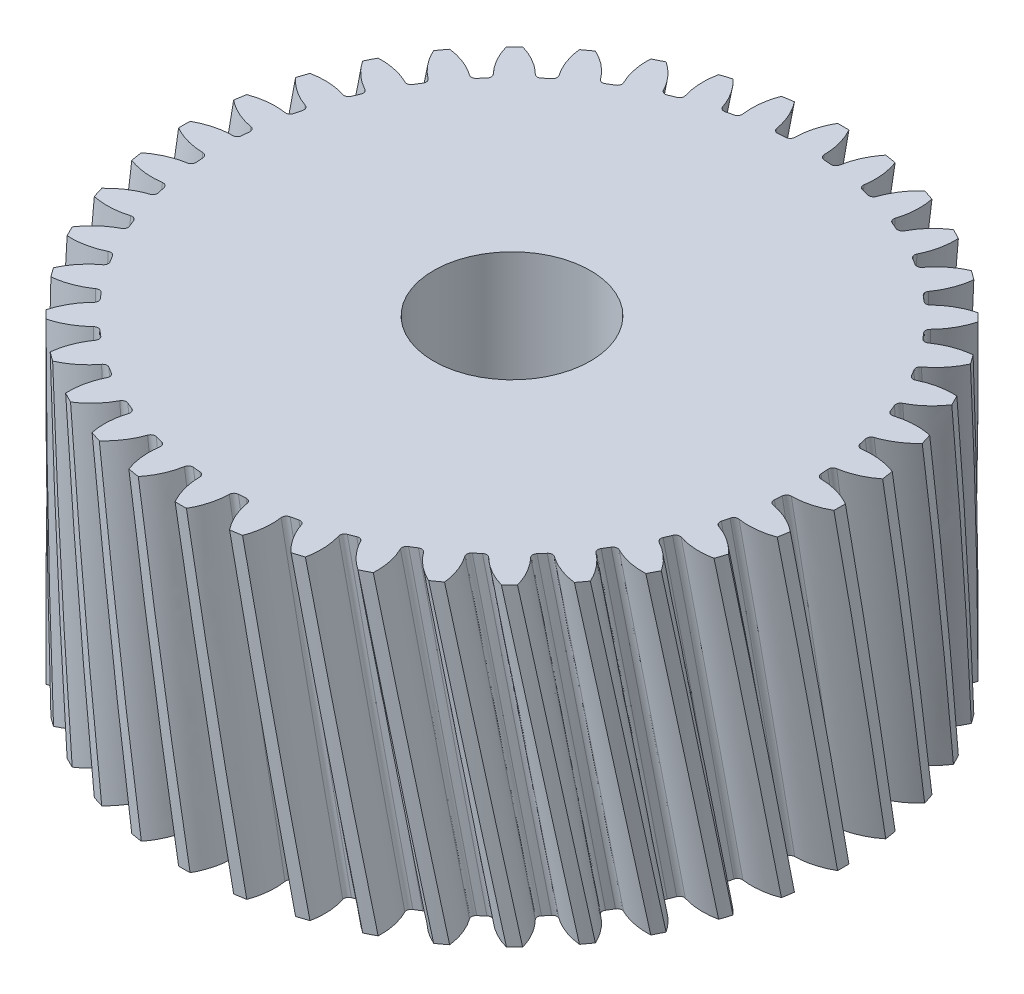
SolidWorks part; units mm, degrees
ref_plane "Front Plane" through (0, 0, 0) normal (0, 0, 1) x (1, 0, 0)
ref_plane "Top Plane" through (0, 0, 0) normal (0, 1, 0) x (1, 0, 0)
ref_plane "Right Plane" through (0, 0, 0) normal (1, 0, 0) x (0, 0, -1)
sketch "Sketch1" plane through (0, 0, 0) normal (0, 1, 0) x (1, 0, 0)
  circle A0 centre (0, 0) radius 20
  circle A1 centre (0, 0) radius 21
  circle A2 centre (0, 0) radius 18.6
  dimension "D1" = 40
  dimension "D2" = 42
  dimension "D3" = 2.4
extrude "Boss-Extrude1" add sketch "Sketch1" along normal mid plane 20 contours A1
sketch "Sketch2" plane through (0, 0, 0) normal (0, 1, 0) x (1, 0, 0)
  line L0 (0, 0) -> (0, 21) construction
  line L1 (-0.7852, 19.9846) -> (0.7852, 19.9846) construction
  line L2 (-0.5197, 18.5927) -> (0, 0) construction
  line L3 (-1.5001, 21.9488) -> (0, 17.8273) construction
  line L4 (0, 0) -> (1.6476, 20.9353) construction
  line L5 (0.7852, 19.9846) -> (2.3507, 19.8614) construction
  circle A0 centre (0, 0) radius 21 construction
  arc A1 (-2.1396, 21.8957) -> (-0.5197, 18.5927) centre (-4.9494, 18.4689) cw
  arc A2 (2.1396, 21.8957) -> (0.5197, 18.5927) centre (4.9494, 18.4689) ccw
  circle A3 centre (0, 0) radius 18.6 construction
  arc A4 (0.5197, 18.5927) -> (-0.5197, 18.5927) centre (0, 0) ccw
  circle A5 centre (0, 0) radius 20 construction
  circle A7 centre (0, 0) radius 22
  arc A8 (2.1396, 21.8957) -> (-2.1396, 21.8957) centre (0, 0) ccw
  circle A9 centre (0, 0) radius 21 construction
  dimension "D2" = 20
  dimension "D3" = 4.5
sketch "Sketch5" plane through (0, 0, 0) normal (0, 0, 1) x (1, 0, 0)
  line L0 (-1.7633, -10) -> (1.7633, 10)
  line L1 (-21, -10) -> (21, -10) construction
  line L2 (21, 10) -> (-21, 10) construction
  line L3 (0, -10) -> (0, 10) construction
  dimension "D1" = 10
curve "Curve1"
sketch "Sketch6" plane through (0, 10, 0) normal (0, 1, 0) x (0.9965, 0, 0.084)
  line L0 (0, 0) -> (0, 21) construction
  line L1 (-0.7852, 19.9846) -> (0.7852, 19.9846) construction
  line L2 (-0.5197, 18.5927) -> (0, 0) construction
  line L3 (-1.5001, 21.9488) -> (0, 17.8273) construction
  line L4 (0, 0) -> (1.6476, 20.9353) construction
  line L5 (0.7852, 19.9846) -> (2.3507, 19.8614) construction
  arc A1 (-2.1396, 21.8957) -> (-0.5197, 18.5927) centre (-4.9494, 18.4689) cw
  arc A2 (2.1396, 21.8957) -> (0.5197, 18.5927) centre (4.9494, 18.4689) ccw
  arc A4 (0.5197, 18.5927) -> (-0.5197, 18.5927) centre (0, 0) ccw
  arc A8 (2.1396, 21.8957) -> (-2.1396, 21.8957) centre (0, 0) ccw
sketch "Sketch7" plane through (0, -10, 0) normal (0, 1, 0) x (0.9965, 0, -0.084)
  line L0 (0, 0) -> (0, 21) construction
  line L1 (-0.7852, 19.9846) -> (0.7852, 19.9846) construction
  line L2 (-0.5197, 18.5927) -> (0, 0) construction
  line L3 (-1.5001, 21.9488) -> (0, 17.8273) construction
  line L4 (0, 0) -> (1.6476, 20.9353) construction
  line L5 (0.7852, 19.9846) -> (2.3507, 19.8614) construction
  arc A1 (-2.1396, 21.8957) -> (-0.5197, 18.5927) centre (-4.9494, 18.4689) cw
  arc A2 (2.1396, 21.8957) -> (0.5197, 18.5927) centre (4.9494, 18.4689) ccw
  arc A4 (0.5197, 18.5927) -> (-0.5197, 18.5927) centre (0, 0) ccw
  arc A8 (2.1396, 21.8957) -> (-2.1396, 21.8957) centre (0, 0) ccw
loft "Cut-Loft1" cut profiles "Sketch6", "Sketch2", "Sketch7" start constraint default end constraint default connector at (3.9705, 10, -21.6387) connector at (2.1396, 0, -21.8957) connector at (0.2936, -10, -21.998)
fillet "Fillet2" radius 0.3 2 edges
pattern_circular "CirPattern3" count 40 over 360 about axis through (0, 10, 0) along (0, -1, 0) of "Cut-Loft1", "Fillet2"
sketch "Sketch8" plane through (0, 10, 0) normal (0, 1, 0) x (1, 0, 0)
  circle A0 centre (0, 0) radius 5
  dimension "D1" = 10
extrude "Cut-Extrude1" cut sketch "Sketch8" against normal through all
equation "\"module\"= 1"
equation "\"number of teeth\" = 40"
equation "\"D1@Sketch1\"=\"module\"*\"number of teeth\""
equation "\"D2@Sketch1\"=(\"number of teeth\"+2) * \"module\""
equation "\"D3@Sketch1\"=\"module\"*if( \"module\"=>1.25,2.25,2.4)"
equation "\"pressure angle\"= 20deg"
equation "\"D2@Sketch2\"=\"pressure angle\""
equation "\"D3@Sketch2\"=180 / \"number of teeth\""
equation "\"helix angle\"= 10deg"
equation "\"D1@Sketch5\"=\"helix angle\""
equation "\"D1@Fillet2\"=\"module\"*.3"
equation "\"D1@CirPattern3\"=\"number of teeth\""
